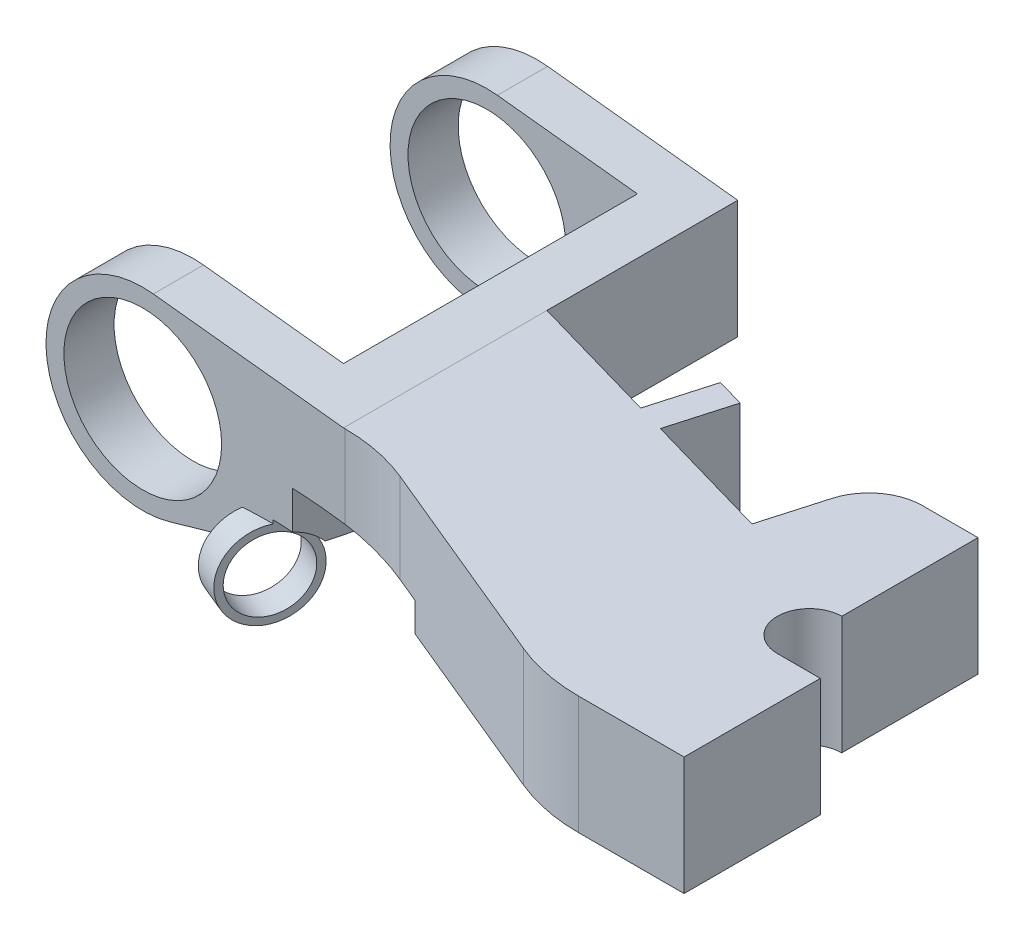
SolidWorks part; units mm, degrees
ref_plane "Спереди" through (0, 0, 0) normal (0, 0, 1) x (1, 0, 0)
ref_plane "Сверху" through (0, 0, 0) normal (0, 1, 0) x (1, 0, 0)
ref_plane "Справа" through (0, 0, 0) normal (1, 0, 0) x (0, 0, -1)
sketch "Эскиз8" plane through (0, 0, 0) normal (0, 1, 0) x (1, 0, 0)
  line L0 (-31.6673, 77.5) -> (-62.0836, 77.5) construction
  line L1 (-85, 43.6529) -> (-6, 21) construction
  line L2 (-106, 13.5) -> (-92.5, 13.5)
  line L3 (-92.5, 13.5) -> (-92.5, 6.5)
  line L4 (-92.5, 6.5) -> (-119.5, 6.5)
  line L6 (-119.5, 6.5) -> (-119.5, 13.5)
  line L7 (-119.5, 13.5) -> (-106, 13.5)
  line L8 (-117, 28.0456) -> (-95, 28.0456) construction
  line L31 (-92.5, 61.5) -> (-119.5, 61.5)
  line L32 (-119.5, 61.5) -> (-119.5, 54.5)
  line L33 (-119.5, 54.5) -> (-92.5, 54.5)
  line L34 (-92.5, 54.5) -> (-92.5, 61.5)
  line L37 (-62.0836, 77.5) -> (-62.0836, 61.5) construction
  line L38 (-62.0836, 61.5) -> (-92.5, 61.5) construction
  line L39 (-11.6673, -9.5) -> (-52.0836, -9.5) construction
  line L44 (-52.0836, -9.5) -> (-52.0836, 6.5) construction
  line L45 (-42.6378, 23.1833) -> (-38.3121, 21.943)
  line L46 (-17.6673, 16.0231) -> (-17.6673, 18.5) construction
  line L47 (-52.0836, 6.5) -> (-92.5, 6.5) construction
  line L48 (-106, 28.0456) -> (-85, 28.0456) construction
  line L52 (-92.5, 54.5) -> (-85, 54.5)
  line L53 (-85, 54.5) -> (-85, 13.5)
  line L54 (-85, 13.5) -> (-92.5, 13.5)
  line L56 (-6, 21) -> (-6, 28) construction
  line L59 (-78, 61.5) -> (-78, 63.0226)
  line L60 (-35.418, 32.0362) -> (-39.7436, 33.2766)
  line L61 (-78, 61.5) -> (-78, 33.3233)
  line L64 (-11.6673, 9.5) -> (-17.6673, 9.5)
  line L65 (-17.6673, 37.5) -> (-17.6673, 18.5) construction
  line L67 (-38.3121, 21.943) -> (-35.418, 32.0362)
  line L68 (-41.1218, 28.4703) -> (-42.6378, 23.1833) construction
  line L69 (-60.3189, 28.2533) -> (-57.4247, 38.3465) construction
  line L70 (-39.7436, 33.2766) -> (-41.1218, 28.4703)
  line L71 (-41.1218, 28.4703) -> (-36.7961, 27.2299)
  line L72 (-42.6378, 23.1833) -> (-78, 33.3233)
  line L79 (-38.3121, 21.943) -> (-17.6673, 16.0231) construction
  line L82 (-35.418, 32.0362) -> (-33.8512, 37.5) construction
  line L83 (-57.665, 38.4155) -> (-61.5101, 39.518)
  line L84 (-57.4247, 38.3465) -> (-57.665, 38.4155)
  line L85 (-57.4247, 38.3465) -> (-57.1844, 38.2776)
  line L86 (-57.1844, 38.2776) -> (-60.0786, 28.1844)
  line L87 (-61.5101, 39.518) -> (-62.8883, 34.7117)
  line L88 (-62.8883, 34.7117) -> (-58.5626, 33.4713)
  line L89 (-57.1844, 38.2776) -> (-53.3394, 37.1751)
  line L90 (-53.3394, 37.1751) -> (-56.2335, 27.0818)
  line L91 (-62.8883, 34.7117) -> (-64.4043, 29.4248) construction
  line L92 (-33.8512, 37.5) -> (-17.6673, 37.5) construction
  circle A1 centre (-106, 28.0456) radius 11
  circle A6 centre (-106, 28.0456) radius 13.5
  arc A8 (-17.6673, 18.5) -> (-17.6673, 9.5) centre (-17.6673, 14) ccw
  spline S0 degree 3 poles (-31.6673, 77.5) (-62.0836, 77.5) (-62.0836, 61.5) (-92.5, 61.5) knots 0 0 0 0 1 1 1 1
  spline S1 degree 3 poles (-11.6673, -9.5) (-52.0836, -9.5) (-52.0836, 6.5) (-92.5, 6.5) knots 0 0 0 0 1 1 1 1
  spline S3 degree 2 poles (-35.418, 32.0362) (-33.8512, 37.5) (-17.6673, 37.5) knots 0 0 0 1 1 1
  point P48 (-60.3189, 28.2533)
sketch "Эскиз10" plane through (0, 0, 0) normal (0, 1, 0) x (1, 0, 0)
  line L0 (-34.4146, 72.312) -> (-60.5171, 61.5) construction
  line L2 (-92.5, 61.5) -> (-78, 61.5)
  line L4 (-78, 34.8837) -> (-78, 61.5)
  line L5 (-20.4853, 37.5) -> (-20.4853, 18.5)
  line L9 (-14.4853, 9.5) -> (-14.4853, -9.5)
  line L11 (-34.1789, -9.5) -> (-14.4853, -9.5)
  line L13 (-92.5, 54.5) -> (-85, 54.5)
  line L14 (-85, 54.5) -> (-85, 13.5)
  line L15 (-85, 13.5) -> (-92.5, 13.5)
  line L21 (-92.5, 6.5) -> (-72.8063, 6.5)
  line L22 (-14.4853, 9.5) -> (-20.4853, 9.5)
  line L23 (-20.4853, 9.5) -> (-20.4853, 18.5) construction
  line L24 (-35.418, 32.0362) -> (-37.8987, 23.3849)
  line L27 (-59.6651, 29.6263) -> (-57.1844, 38.2776)
  line L28 (-57.1844, 38.2776) -> (-53.3394, 37.1751)
  line L29 (-53.3394, 37.1751) -> (-55.8201, 28.5237)
  line L31 (-53.4926, -9.5) -> (-53.4926, 6.5) construction
  line L32 (-92.5, 61.5) -> (-119.5, 61.5)
  line L34 (-92.5, 54.5) -> (-119.5, 54.5)
  line L35 (-119.5, 61.5) -> (-119.5, 54.5)
  line L36 (-92.5, 13.5) -> (-119.5, 13.5)
  line L38 (-92.5, 6.5) -> (-119.5, 6.5)
  line L39 (-119.5, 13.5) -> (-119.5, 6.5)
  line L40 (-78, 34.8837) -> (-59.6651, 29.6263)
  line L41 (-53.4926, -1.5) -> (-72.8063, 6.5)
  line L42 (-53.4926, -1.5) -> (-34.1789, -9.5)
  line L43 (-55.8201, 28.5237) -> (-37.8987, 23.3849)
  line L44 (-20.4853, 37.5) -> (-28.1673, 37.5)
  line L45 (-35.418, 32.0362) -> (-28.1673, 29.9571) construction
  line L46 (-28.1673, 37.5) -> (-28.1673, 29.9571) construction
  arc A0 (-20.4853, 18.5) -> (-20.4853, 9.5) centre (-20.4853, 14) ccw
  arc A2 (-35.418, 32.0362) -> (-28.1673, 37.5) centre (-28.1673, 29.9571) cw
extrude "Бобышка-Вытянуть1" add sketch "Эскиз10" along normal mid plane 27 separate body contours L24 L29 L28 L27 L4 L32 L35 L34 L13 L14 L15 L36 L39 L38 region at (-59.1919, 0, -19.6134)
sketch "Эскиз11" plane through (0, 0, 0) normal (0, 0, 1) x (1, 0, 0)
  line L10 (-11.6673, -6) -> (-11.6673, 10.5)
  line L16 (-106, 0) -> (-11.6673, 0) construction
  line L31 (-11.6673, 10.5) -> (-78, 10.5)
  line L50 (-119.5, 13.5) -> (-11.6673, 13.5)
  line L51 (-119.5, 13.5) -> (-119.5, -13.5)
  line L52 (-119.5, -13.5) -> (-11.6673, -13.5)
  line L53 (-11.6673, 13.5) -> (-11.6673, -13.5)
  line L55 (-78, 10.5) -> (-78, -6)
  line L56 (-78, -6) -> (-11.6673, -6)
  line L57 (-78, -6) -> (-102.2714, -12.9749)
  line L58 (-78, 10.5) -> (-104.5232, 13.419)
  circle A2 centre (-106, 0) radius 11
  circle A5 centre (-106, 0) radius 13.5
extrude "Вырез-Вытянуть1" cut sketch "Эскиз11" against normal through all both and the other way through all contours A2 | A5 L51 L52 | A5 L50 L51 | L52 L53 | L50 L53 region at (-51.7306, -9.9565, 0) region at (-52.0379, 12.0853, 0) region at (-116.4845, -10.4845, 0) region at (-116.4845, 10.4845, 0) region at (-106, 0, 0)
sketch "Эскиз12" plane through (-62.9818, 0, -18.0597) normal (-0.9613, 0, -0.2756) x (-0.2756, 0, 0.9613)
  line L0 (-18.5327, 0) -> (-18.5327, -6) construction
  line L1 (-21.0327, 0) -> (-18.5327, 0) construction
  line L2 (-21.0327, -6) -> (-12.0327, -6) construction
  circle A0 centre (-18.5327, 0) radius 2.5
extrude "Бобышка-Вытянуть2" add sketch "Эскиз12" along normal blind 4.5
sketch "Эскиз13" plane through (-41.2153, 0, -11.8183) normal (-0.9613, 0, -0.2756) x (-0.2756, 0, 0.9613)
  line L0 (-21.0327, 0) -> (-18.5327, 0) construction
  line L2 (-18.5327, 0) -> (-18.5327, -6) construction
  line L3 (-12.0327, -6) -> (-21.0327, -6) construction
  circle A0 centre (-18.5327, 0) radius 2.5
  point P5 (0, 0)
extrude "Бобышка-Вытянуть3" add sketch "Эскиз13" along normal blind 4.5
fillet "Скругление1" radius 25 2 edges at (-34.1789, 2.25, 9.5) (-72.8063, 2.25, -6.5)
sketch "Эскиз15" plane through (-80.9415, 0, -33.5271) normal (-0.9239, 0, -0.3827) x (-0.3827, 0, 0.9239)
  circle A0 centre (27.9359, -12) radius 5
  circle A1 centre (27.9359, -12) radius 6
extrude "Бобышка-Вытянуть4" add sketch "Эскиз15" against normal blind 4
sketch3d "Трехмерный эскиз2"
  line L0 (-75.2961, -2.5, 5.5433) -> (-82.6968, -2.5, 2.4778)
  line L1 (-82.6968, -2.5, 2.4778) -> (-78.1046, -21.5, -8.6087)
ref_plane "Плоскость3" through (-9.7155, -16.0344, 23.4553) normal (-0.3236, -0.534, 0.7811) x (0.9462, -0.1826, 0.2671)
sketch "Эскиз18" plane through (-9.7155, -16.0344, 23.4553) normal (-0.3236, -0.534, 0.7811) x (0.9462, -0.1826, 0.2671)
  line L0 (-82.0108, -7.1077) -> (-81.0339, -6.8941)
  line L3 (-81.0339, -6.8941) -> (-81.2236, -6.0364)
  line L4 (-83.4754, -7.4316) -> (-83.9636, -7.5396)
  line L5 (-80.5962, -3.4484) -> (-79.6779, -2.2435)
  line L6 (-83.9636, -7.5396) -> (-87.8692, -8.4035) construction
  line L7 (-77.1301, -0.6655) -> (-69.3087, 1.0645)
  line L9 (-62.7353, -0.8951) -> (-62.0049, -4.1972)
  line L18 (-69.4167, 1.5527) -> (-63.0749, 2.9554)
  line L20 (-62.2471, -0.7871) -> (-63.0749, 2.9554)
  line L22 (-69.3087, 1.0645) -> (-69.4167, 1.5527) construction
  line L24 (-62.7353, -0.8951) -> (-62.2471, -0.7871) construction
  line L32 (-62.2471, -0.7871) -> (-61.5167, -4.0892)
  line L39 (-83.4754, -7.4316) -> (-82.0108, -7.1077)
  line L41 (-77.1301, -0.6655) -> (-77.2381, -0.1773) construction
  line L42 (-77.2381, -0.1773) -> (-69.4167, 1.5527)
  line L43 (-73.2194, 0.1995) -> (-73.3274, 0.6877) construction
  line L45 (-77.2381, -0.1773) -> (-82.7615, -1.399)
  line L46 (-81.2236, -6.0364) -> (-81.7118, -6.1443) construction
  line L47 (-83.9636, -7.5396) -> (-84.0716, -7.0514)
  line L48 (-84.0716, -7.0514) -> (-81.6306, -6.5115)
  line L49 (-81.6306, -6.5115) -> (-82.7615, -1.399)
  line L50 (-80.5962, -3.4484) -> (-80.9938, -3.1453) construction
  line L51 (-79.6779, -2.2435) -> (-80.0755, -1.9404) construction
  line L52 (-80.137, -2.8459) -> (-80.5347, -2.5428) construction
  line L53 (-80.9938, -3.1453) -> (-80.0755, -1.9404) construction
  line L54 (-69.3087, 1.0645) -> (-68.5889, -2.1898) construction
  line L55 (-62.7353, -0.8951) -> (-68.5889, -2.1898) construction
  line L56 (-83.9636, -7.5396) -> (-82.6678, -13.398)
  line L57 (-82.6678, -13.398) -> (-60.5403, -8.5037)
  line L58 (-61.5167, -4.0892) -> (-60.5403, -8.5037)
  spline S1 degree 3 poles (-81.2236, -6.0364) (-81.4199, -5.1489) (-81.1996, -4.2401) (-80.5962, -3.4484) knots 0 0 0 0 1 1 1 1 weights 1 0.949253 0.949253 1
  spline S3 degree 3 poles (-79.6779, -2.2435) (-79.0744, -1.4518) (-78.1798, -0.8977) (-77.1301, -0.6655) knots 0 0 0 0 1 1 1 1 weights 1 0.949253 0.949253 1
  spline S5 degree 3 poles (-69.3087, 1.0645) (-65.7664, 1.848) (-63.0107, 1.0266) (-62.7353, -0.8951) knots 0 0 0 0 1 1 1 1 weights 1 0.79515 0.79515 1
revolve "Вырез-Повернуть2" cut sketch "Эскиз18" angle 360 about L57 region at (-78.1506, -7.1809, 1.161)
sketch "Эскиз19" plane through (-77.246, 0, -31.9963) normal (0.9239, 0, 0.3827) x (0.3827, 0, -0.9239)
  line L0 (-33.9359, -2.5) -> (-21.9359, -21.5) construction
  circle A0 centre (-27.9359, -12) radius 5
extrude "Вырез-Вытянуть3" cut sketch "Эскиз19" against normal blind 4
sketch "Эскиз20" plane through (-80.9415, 0, -33.5271) normal (0.9239, 0, 0.3827) x (0.3827, 0, -0.9239)
  line L0 (-33.9359, -2.5) -> (-21.9359, -21.5) construction
  circle A0 centre (-27.9359, -12) radius 5
extrude "Вырез-Вытянуть4" cut sketch "Эскиз20" against normal blind 0.5
